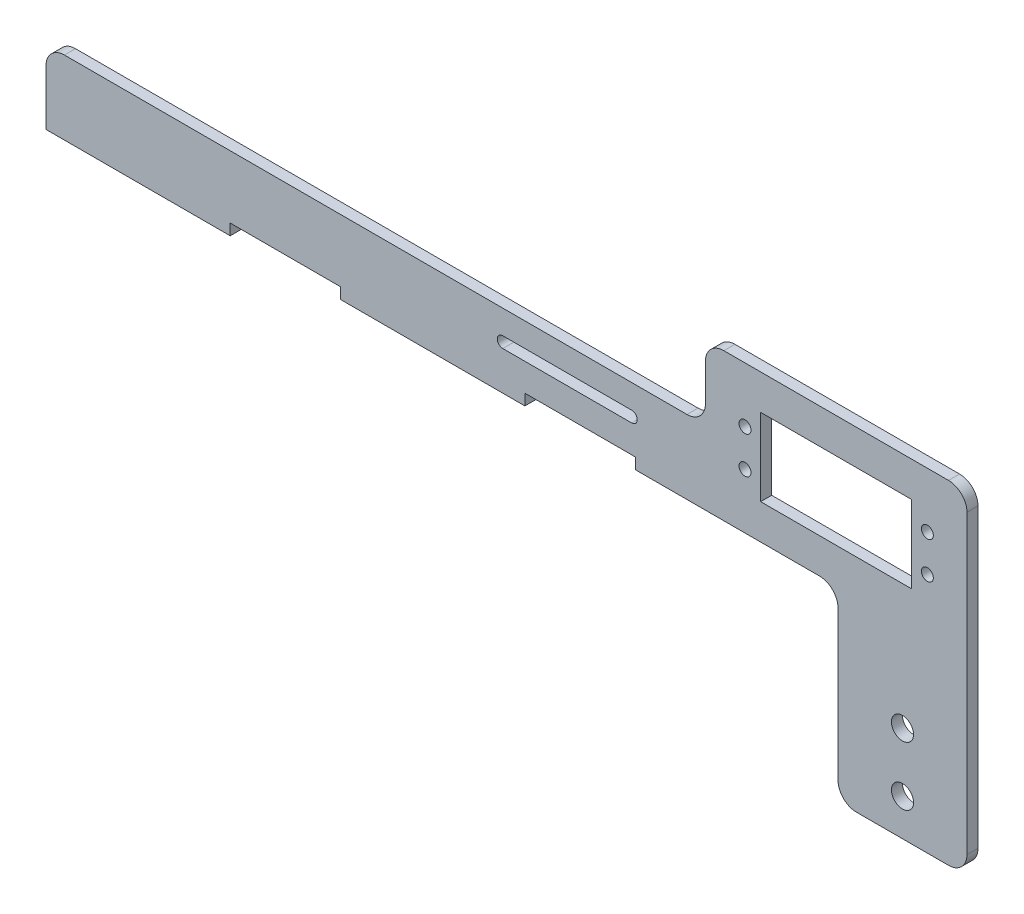
SolidWorks part; units mm, degrees
ref_plane "Plano frontal" through (0, 0, 0) normal (0, 0, 1) x (1, 0, 0)
ref_plane "Plano superior" through (0, 0, 0) normal (0, 1, 0) x (1, 0, 0)
ref_plane "Plano direito" through (0, 0, 0) normal (1, 0, 0) x (0, 0, -1)
sketch "Esboço1" plane through (0, 0, 0) normal (0, 0, 1) x (1, 0, 0)
  line L0 (194, 0) -> (235, 0) construction
  line L1 (215, -20) -> (160, -20)
  line L2 (250, -20) -> (250, 20)
  line L3 (250, 20) -> (179, 20)
  line L4 (0, -20) -> (0, 0)
  line L5 (194, 10.5) -> (235, 10.5)
  line L6 (194, 10.5) -> (194, -10.5)
  line L7 (194, -10.5) -> (235, -10.5)
  line L8 (235, 10.5) -> (235, -10.5)
  line L9 (214.5, 10.5) -> (214.5, -10.5) construction
  line L10 (0, 0) -> (179, 0)
  line L11 (179, 0) -> (179, 20)
  line L12 (250, 0) -> (184.4373, 0) construction
  line L13 (50, -20) -> (50, -17)
  line L14 (50, -17) -> (80, -17)
  line L15 (80, -17) -> (80, -20)
  line L16 (130, -20) -> (130, -17)
  line L17 (130, -17) -> (160, -17)
  line L18 (160, -17) -> (160, -20)
  line L19 (50, -20) -> (0, -20)
  line L20 (130, -20) -> (80, -20)
  line L21 (124, -8) -> (159, -8) construction
  line L22 (124, -6.5) -> (159, -6.5)
  line L23 (124, -9.5) -> (159, -9.5)
  line L26 (215, -20) -> (215, -70.5)
  line L27 (215, -70.5) -> (250, -70.5)
  line L28 (250, -20) -> (250, -70.5)
  circle A0 centre (189.75, 5) radius 1.625
  circle A1 centre (239.25, 5) radius 1.625
  circle A2 centre (239.25, -5) radius 1.625
  circle A3 centre (189.75, -5) radius 1.625
  arc A5 (124, -6.5) -> (124, -9.5) centre (124, -8) ccw
  arc A6 (159, -9.5) -> (159, -6.5) centre (159, -8) ccw
  circle A7 centre (232.5, -60.5) radius 3
  circle A8 centre (232.5, -44.5) radius 3
  point P36 (141.5, -8)
  dimension "D8" = 3.25
  dimension "D9" = 10
  dimension "D19" = 1.5
  dimension "D27" = 6
  dimension "D29" = 10
  dimension "D30" = 6
  dimension "D3" = 41
  dimension "D4" = 15
  dimension "D5" = 21
  dimension "D6" = 9.5
  dimension "D7" = 49.5
  dimension "D10" = 20
  dimension "D11" = 15
  dimension "D12" = 179
  dimension "D13" = 50
  dimension "D14" = 30
  dimension "D15" = 3
  dimension "D16" = 50
  dimension "D17" = 30
  dimension "D18" = 3
  dimension "D20" = 8
  dimension "D21" = 35
  dimension "D22" = 20
  dimension "D23" = 71
  dimension "D24" = 40
  dimension "D25" = 9.5
  dimension "D26" = 35
  dimension "D28" = 50.5
  dimension "D31" = 16
extrude "Ressalto-extrusão1" add sketch "Esboço1" along normal blind 3 contours L20 L16 L17 L18 L1 L2 L3 L11 L10 L4 L19 L13 L14 L15 A1 A0 L5 L8 L7 L6 A2 A3 region at (158.5131, -15.6355, 0)
fillet "Filete1" radius 5 7 edges at (215, -20, 1.5) (215, -70.5, 1.5) (250, -70.5, 1.5) (250, 20, 1.5) (179, 20, 1.5) (179, 0, 1.5) (0, 0, 1.5)
